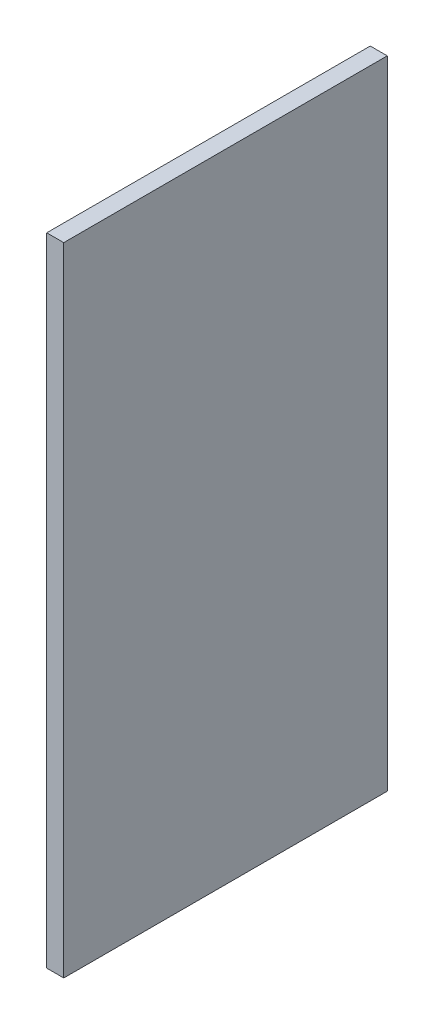
SolidWorks part; units mm, degrees
ref_plane "Спереди" through (0, 0, 0) normal (0, 0, 1) x (1, 0, 0)
ref_plane "Сверху" through (0, 0, 0) normal (0, 1, 0) x (1, 0, 0)
ref_plane "Справа" through (0, 0, 0) normal (1, 0, 0) x (0, 0, -1)
sketch "Эскиз1" plane through (0, 0, 0) normal (0, 1, 0) x (1, 0, 0)
  line L1 (0, 0) -> (5, 0)
  line L2 (0, 0) -> (0, -95)
  line L3 (0, -95) -> (5, -95)
  line L4 (5, 0) -> (5, -95)
  dimension "D1" = 5
  dimension "D2" = 95
extrude "Бобышка-Вытянуть1" add sketch "Эскиз1" along normal blind 187
